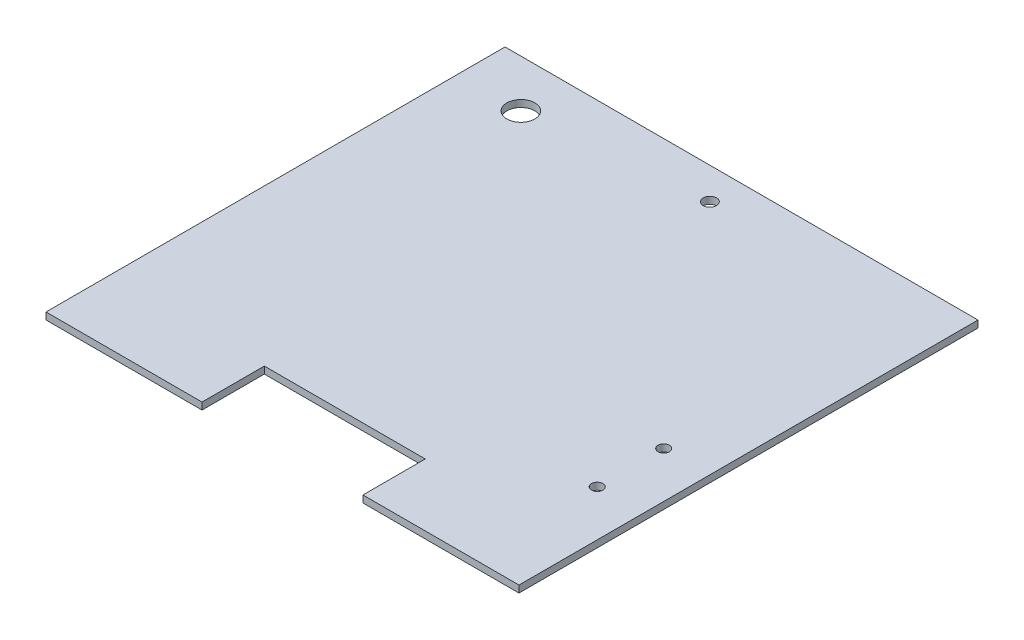
SolidWorks part; units mm, degrees
ref_plane "Front Plane" through (0, 0, 0) normal (0, 0, 1) x (1, 0, 0)
ref_plane "Top Plane" through (0, 0, 0) normal (0, 1, 0) x (1, 0, 0)
ref_plane "Right Plane" through (0, 0, 0) normal (1, 0, 0) x (0, 0, -1)
sketch "Sketch1" plane through (0, 0, 0) normal (0, 1, 0) x (1, 0, 0)
  line L1 (-94.869, -92.075) -> (94.869, -92.075)
  line L2 (-94.869, -92.075) -> (-94.869, 92.075)
  line L3 (-94.869, 92.075) -> (94.869, 92.075)
  line L4 (94.869, -92.075) -> (94.869, 92.075)
  line L5 (-94.869, -92.075) -> (94.869, 92.075) construction
  line L6 (-94.869, 92.075) -> (94.869, -92.075) construction
  point P0 (0, 0)
  dimension "D1" = 189.738
  dimension "D2" = 184.15
extrude "Boss-Extrude1" add sketch "Sketch1" along normal blind 2.794
sketch "Sketch2" plane through (0, 2.794, 0) normal (0, 1, 0) x (1, 0, 0)
  line L2 (94.869, 92.075) -> (-94.869, 92.075) construction
  circle A0 centre (0, 79.375) radius 2.6797
  point P2 (0, 0)
  dimension "D1" = 5.3594
  dimension "D2" = 12.7
extrude "Cut-Extrude1" cut sketch "Sketch2" against normal through all
sketch "Sketch3" plane through (0, 2.794, 0) normal (0, 1, 0) x (1, 0, 0)
  line L0 (0, -92.075) -> (-32.28, -92.075)
  line L1 (-94.869, -92.075) -> (94.869, -92.075) construction
  line L2 (-32.28, -92.075) -> (-32.28, -67.075)
  line L3 (-32.28, -67.075) -> (32.28, -67.075)
  line L4 (32.28, -67.075) -> (32.28, -92.075)
  line L5 (32.28, -92.075) -> (0, -92.075)
  point P5 (0, -67.075)
  dimension "D1" = 64.56
  dimension "D3" = 25
extrude "Cut-Extrude2" cut sketch "Sketch3" against normal through all
sketch "Sketch5" plane through (0, 2.794, 0) normal (0, 1, 0) x (1, 0, 0)
  line L4 (40.513, 2.9718) -> (85.979, 2.9718)
  line L5 (85.979, 2.9718) -> (85.979, -60.325)
  line L6 (85.979, -60.325) -> (40.513, -60.325)
  line L7 (40.513, -60.325) -> (40.513, 2.9718)
  line L8 (94.869, -92.075) -> (94.869, 92.075) construction
  line L9 (32.28, -92.075) -> (94.869, -92.075) construction
  line L10 (94.869, 92.075) -> (-94.869, 92.075) construction
  line L15 (-94.869, 92.075) -> (-94.869, -92.075) construction
  circle A2 centre (76.454, -15.596) radius 2.286
  circle A3 centre (76.454, -42.266) radius 2.286
  circle A4 centre (-69.469, 73.025) radius 5.6134
  dimension "D3" = 31.75
  dimension "D5" = 25.4
  dimension "D6" = 11.2268
  dimension "D10" = 4.572
  dimension "D11" = 18.059
  dimension "D12" = 26.67
  dimension "D13" = 18.5678
  dimension "D14" = 9.525
  dimension "D4" = 19.05
  dimension "D2" = 8.89
  dimension "D8" = 45.466
  dimension "D9" = 63.2968
extrude "Cut-Extrude3" cut sketch "Sketch5" against normal through all contours A2 | A4 | A3
